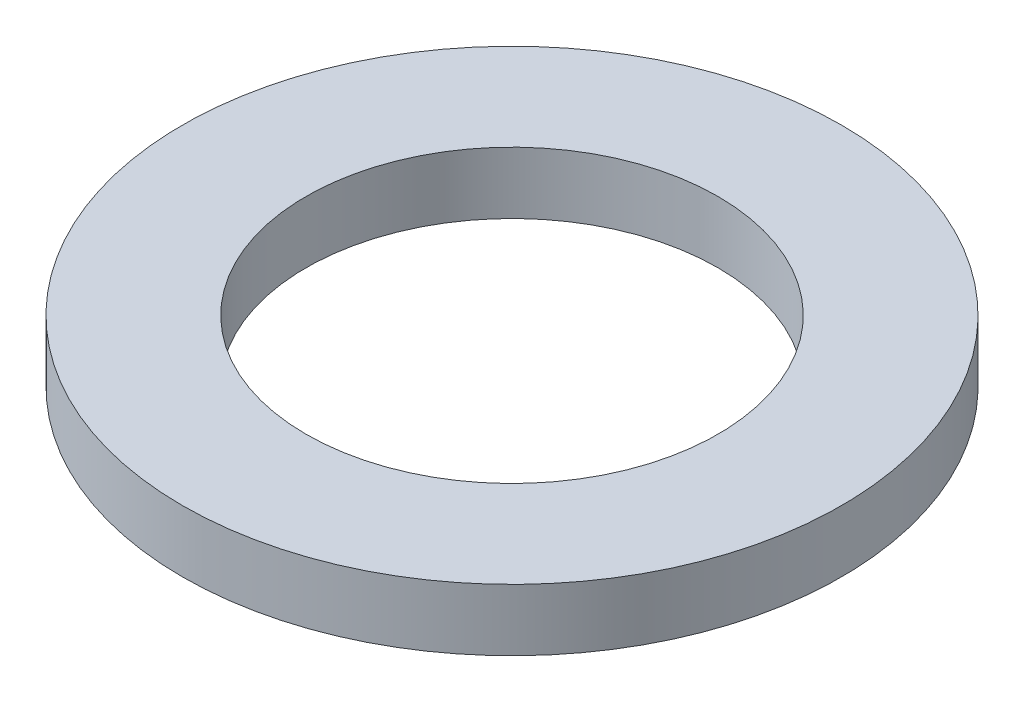
SolidWorks part; units mm, degrees
ref_plane "Front Plane" through (0, 0, 0) normal (0, 0, 1) x (1, 0, 0)
ref_plane "Top Plane" through (0, 0, 0) normal (0, 1, 0) x (1, 0, 0)
ref_plane "Right Plane" through (0, 0, 0) normal (1, 0, 0) x (0, 0, -1)
sketch "Sketch1" plane through (0, 0, 0) normal (0, 1, 0) x (1, 0, 0)
  circle A0 centre (0, 0) radius 80
  dimension "FLANGE_OD" = 160
extrude "Boss-Extrude1" add sketch "Sketch1" along normal blind 15
sketch "Sketch2" plane through (0, 0, 0) normal (0, 1, 0) x (1, 0, 0)
  circle A0 centre (0, 0) radius 50
  dimension "BORE_D" = 100
extrude "Cut-Extrude1" cut sketch "Sketch2" along normal through all
sketch "Sketch3" plane through (0, 15, 0) normal (0, 1, 0) x (1, 0, 0)
  circle A0 centre (0, 0) radius 30.6632 construction
  circle A1 centre (-30.6632, 0) radius 2.8284
  dimension "BOLT_D" = 5.6569
  dimension "BOLT_PCD" = 61.3263
extrude "Cut-Extrude2" cut sketch "Sketch3" against normal blind 12.4203 rebuild error yes
pattern_circular "CirPattern1" count 6 over 360 rebuild error yes
